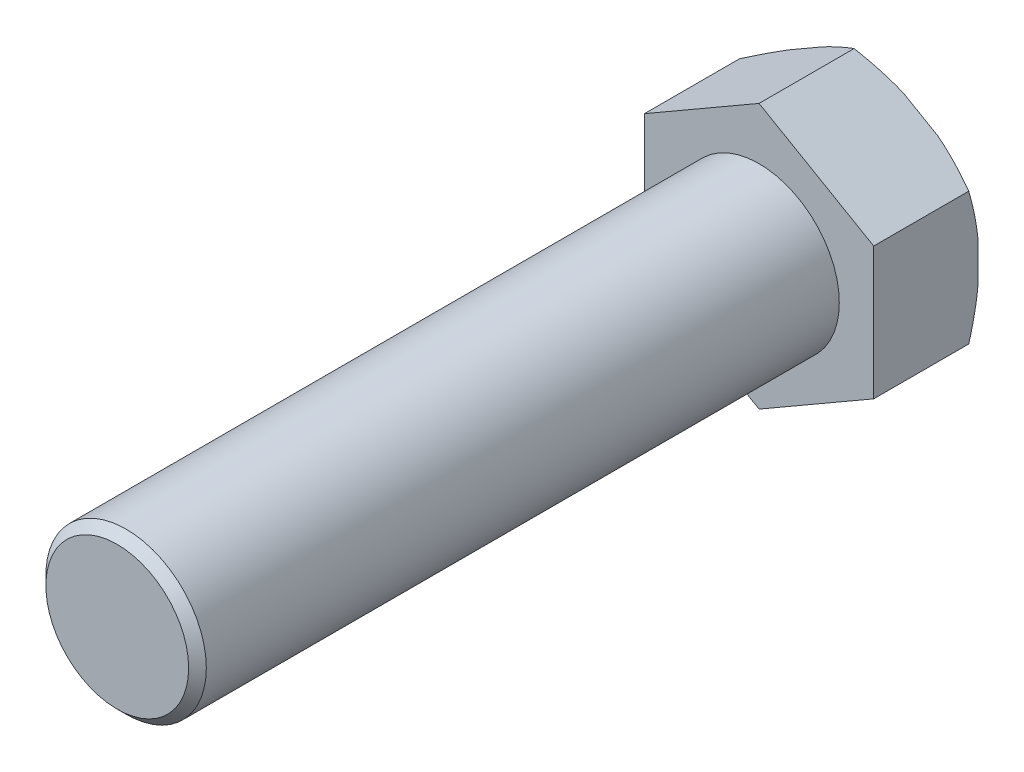
SolidWorks part; units mm, degrees
material "AISI 304"
ref_plane "Спереди" through (0, 0, 0) normal (0, 0, 1) x (1, 0, 0)
ref_plane "Сверху" through (0, 0, 0) normal (0, 1, 0) x (1, 0, 0)
ref_plane "Справа" through (0, 0, 0) normal (1, 0, 0) x (0, 0, -1)
sketch "Эскиз1" plane through (0, 0, 0) normal (0, 0, 1) x (1, 0, 0)
  line L1 (0, 16.5) -> (-14.2894, 8.25)
  line L2 (-14.2894, 8.25) -> (-14.2894, -8.25)
  line L3 (-14.2894, -8.25) -> (0, -16.5)
  line L4 (0, -16.5) -> (14.2894, -8.25)
  line L5 (14.2894, -8.25) -> (14.2894, 8.25)
  line L6 (14.2894, 8.25) -> (0, 16.5)
  circle A0 centre (0, 0) radius 10
  circle A1 centre (0, 0) radius 16.5 construction
  dimension "D1" = 20
  dimension "D2" = 33
extrude "Бобышка-Вытянуть1" add sketch "Эскиз1" along normal blind 80 contours A0 region at (0, 0, 0)
cosmetic thread "Условное изображение резьбы1" parameters "D1"=50, "D2"=17.797
extrude "Бобышка-Вытянуть2" add sketch "Эскиз1<4>" against normal blind 13 separate body contours L6 L1 L2 L3 L4 L5
sketch "Эскиз1<4>" plane through (0, 0, 0) normal (0, 0, 1) x (1, 0, 0) same geometry as "Эскиз1"
sketch "Эскиз3" plane through (0, 0, 0) normal (1, 0, 0) x (0, 0, -1)
  line L0 (13, 24.5) -> (13, 14.5)
  line L2 (13, 14.5) -> (7.2265, 24.5)
  line L3 (7.2265, 24.5) -> (13, 24.5)
  line L4 (0, 0) -> (50000, 0) construction
  line L8 (13, 8.25) -> (13, 16.5) construction
  line L9 (13, 16.5) -> (0, 16.5) construction
  dimension "D1" = 10
  dimension "D2" = 30
  dimension "D3" = 2
revolve "Вырез-Повернуть1" cut sketch "Эскиз3" angle 360 about L4
chamfer "Фаска1" distance 1.1015 angle 45 1 edges at (10, 0, 80)
